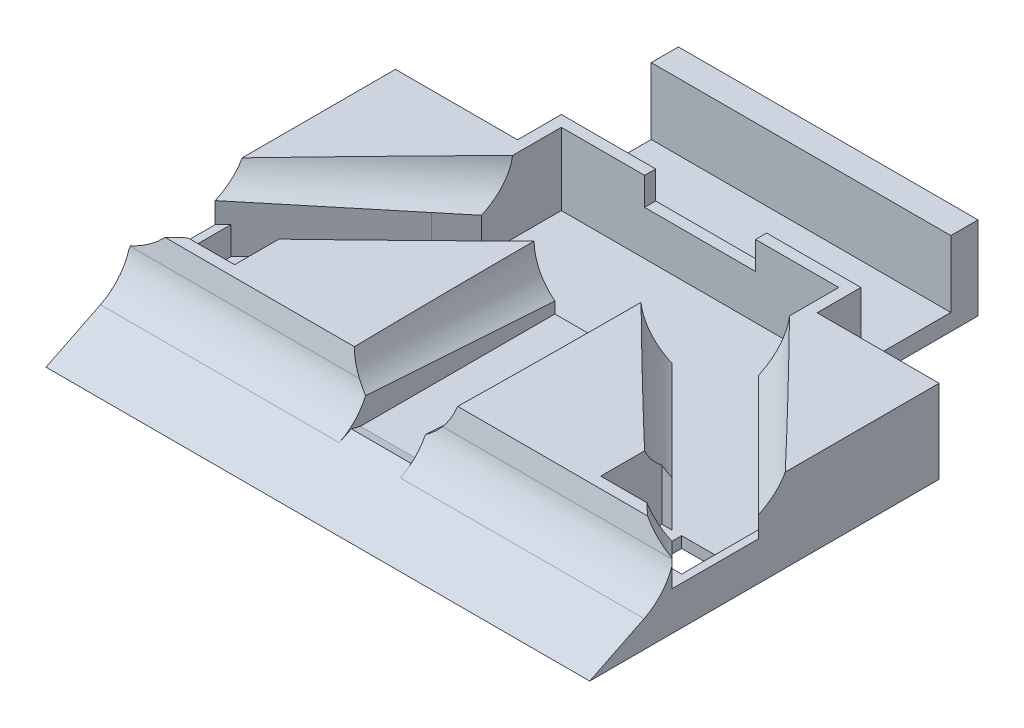
SolidWorks part; units mm, degrees
ref_plane "Front Plane" through (0, 0, 0) normal (0, 0, 1) x (1, 0, 0)
ref_plane "Top Plane" through (0, 0, 0) normal (0, 1, 0) x (1, 0, 0)
ref_plane "Right Plane" through (0, 0, 0) normal (1, 0, 0) x (0, 0, -1)
sketch "Sketch1" plane through (0, 0, 0) normal (0, 1, 0) x (1, 0, 0)
  line L1 (-41.0843, 19.8343) -> (56.9157, 19.8343)
  line L2 (-41.0843, 19.8343) -> (-41.0843, -70.1657)
  line L3 (-41.0843, -70.1657) -> (56.9157, -70.1657)
  line L4 (56.9157, 19.8343) -> (56.9157, -70.1657)
  dimension "D1" = 98
  dimension "D2" = 90
extrude "Boss-Extrude1" add sketch "Sketch1" along normal blind 15
sketch "Sketch3" plane through (0, 15, 0) normal (0, 1, 0) x (1, 0, 0)
  line L0 (-41.0843, -35.1657) -> (-6.0843, -70.1657)
  line L1 (-41.0843, 19.8343) -> (-41.0843, -70.1657) construction
  line L2 (-41.0843, -70.1657) -> (56.9157, -70.1657) construction
  line L3 (-6.0843, -70.1657) -> (-41.0843, -70.1657)
  line L4 (-41.0843, -70.1657) -> (-41.0843, -35.1657)
  line L5 (21.9157, -70.1657) -> (56.9157, -35.1657)
  line L6 (56.9157, -70.1657) -> (56.9157, 19.8343) construction
  line L7 (56.9157, -35.1657) -> (56.9157, -70.1657)
  line L8 (56.9157, -70.1657) -> (21.9157, -70.1657)
  dimension "D1" = 35
  dimension "D2" = 35
  dimension "D3" = 35
extrude "Cut-Extrude1" cut sketch "Sketch3" against normal blind 15
sketch "Sketch4" plane through (0, 15, 0) normal (0, 1, 0) x (1, 0, 0)
  line L0 (-41.0843, -35.1657) -> (-32.2419, -26.3233)
  line L1 (-32.2419, -26.3233) -> (-41.0843, -17.4808)
  line L2 (-41.0843, 19.8343) -> (-41.0843, -35.1657) construction
  line L3 (-41.0843, -17.4808) -> (-41.0843, -35.1657)
  line L4 (56.9157, -17.4808) -> (48.0733, -26.3233)
  line L5 (56.9157, -35.1657) -> (56.9157, 19.8343) construction
  line L6 (48.0733, -26.3233) -> (56.9157, -35.1657)
  line L7 (56.9157, -35.1657) -> (56.9157, -17.4808)
extrude "Cut-Extrude2" cut sketch "Sketch4" against normal blind 15
sketch "Sketch5" plane through (-2.9593, 0, -2.9593) normal (-0.7071, 0, -0.7071) x (-0.7071, 0, 0.7071)
  line L0 (53.9169, 0) -> (52.9169, 15)
  line L1 (53.9169, 15) -> (41.4118, 15) construction
  line L2 (53.9169, 15) -> (52.9169, 15)
  line L4 (53.9169, 15) -> (53.9169, 0)
  dimension "D1" = 1
extrude "Cut-Extrude5" cut sketch "Sketch5" against normal blind 100
sketch "Sketch8" plane through (10.875, 0, -10.875) normal (0.7071, 0, -0.7071) x (-0.7071, 0, -0.7071)
  line L0 (-65.1114, 0) -> (-64.1114, 15)
  line L1 (-52.6063, 15) -> (-65.1114, 15) construction
  line L2 (-64.1114, 15) -> (-65.1114, 15)
  line L3 (-65.1114, 15) -> (-65.1114, 0)
  dimension "D1" = 1
extrude "Cut-Extrude6" cut sketch "Sketch8" against normal blind 100
sketch "Sketch9" plane through (45.837, 4.3215, 45.837) normal (0.7055, 0.0665, 0.7055) x (0.7087, -0.0662, -0.7024)
  line L0 (15.6331, -3.3008) -> (-33.7552, -6.5861) construction
  circle A0 centre (-0.3647, 13.6748) radius 9.5
  dimension "D1" = 18
  dimension "D2" = 15
extrude "Cut-Extrude7" cut sketch "Sketch9" against normal blind 45
sketch "Sketch10" plane through (-37.9563, 3.5786, 37.9563) normal (-0.7055, 0.0665, 0.7055) x (0.7087, 0.0662, 0.7024)
  line L0 (44.9744, -6.5861) -> (-4.4139, -3.3008) construction
  circle A0 centre (11.452, 13.6836) radius 9.5
  dimension "D1" = 18
  dimension "D2" = 15
extrude "Cut-Extrude8" cut sketch "Sketch10" against normal blind 45
sketch "Sketch12" plane through (10.875, 0, -10.875) normal (0.7071, 0, -0.7071) x (-0.7071, 0, -0.7071)
  line L0 (-65.1114, 0) -> (-64.1114, 15)
  line L1 (-64.1114, 15) -> (-65.1114, 15)
  line L2 (-65.1114, 15) -> (-65.1114, 0)
  dimension "D1" = 1
extrude "Boss-Extrude3" add sketch "Sketch12" against normal blind 100
sketch "Sketch13" plane through (-2.9593, 0, -2.9593) normal (-0.7071, 0, -0.7071) x (-0.7071, 0, 0.7071)
  line L0 (53.9169, 0) -> (52.9169, 15)
  line L1 (52.9169, 15) -> (53.9169, 15)
  line L2 (53.9169, 15) -> (53.9169, 0)
  dimension "D1" = 1
extrude "Boss-Extrude4" add sketch "Sketch13" against normal blind 100
sketch "Sketch14" plane through (0, 15, 0) normal (0, 1, 0) x (1, 0, 0)
  line L1 (-6.0843, -70.1657) -> (48.4536, -70.1657)
  line L2 (-6.0843, -70.1657) -> (-6.0843, -107.5994)
  line L3 (-6.0843, -107.5994) -> (48.4536, -107.5994)
  line L4 (48.4536, -70.1657) -> (48.4536, -107.5994)
extrude "Cut-Extrude9" cut sketch "Sketch14" against normal blind 100
sketch "Sketch15" plane through (0, 15, 0) normal (0, 1, 0) x (1, 0, 0)
  line L2 (3.5432, -108.6479) -> (-33.6782, -108.6479)
  line L3 (3.5432, -108.6479) -> (3.5432, -76.6689)
  line L4 (3.5432, -76.6689) -> (-33.6782, -76.6689)
  line L5 (-33.6782, -108.6479) -> (-33.6782, -76.6689)
extrude "Cut-Extrude10" cut sketch "Sketch15" against normal blind 100
sketch "Sketch16" plane through (0, 15, 0) normal (0, 1, 0) x (1, 0, 0)
  line L0 (-6.0843, -70.1657) -> (-35.8986, -70.1657)
  line L1 (-41.0843, -35.1657) -> (-41.0843, -70.1657)
  line L2 (-41.0843, -70.1657) -> (-35.8986, -70.1657)
  line L3 (-41.0843, -35.1657) -> (-6.0843, -70.1657)
extrude "Boss-Extrude5" add sketch "Sketch16" against normal blind 15
sketch "Sketch17" plane through (0, 15, 0) normal (0, 1, 0) x (1, 0, 0)
  line L0 (21.9157, -70.1657) -> (49.8862, -70.1657)
  line L1 (56.9157, -35.1657) -> (56.9157, -70.1657)
  line L2 (56.9157, -70.1657) -> (49.8862, -70.1657)
  line L3 (21.9157, -70.1657) -> (56.9157, -35.1657)
extrude "Boss-Extrude6" add sketch "Sketch17" against normal blind 15
sketch "Sketch18" plane through (0, 15, 0) normal (0, 1, 0) x (1, 0, 0)
  line L0 (48.0733, -26.3233) -> (56.9157, -17.4808)
  line L1 (56.9157, -17.4808) -> (56.9157, -35.1657)
  line L2 (56.9157, -35.1657) -> (48.0733, -26.3233)
  line L3 (-41.0843, -35.1657) -> (-41.0843, -17.4808)
  line L4 (-41.0843, -17.4808) -> (-32.2419, -26.3233)
  line L5 (-32.2419, -26.3233) -> (-41.0843, -35.1657)
extrude "Boss-Extrude7" add sketch "Sketch18" against normal blind 15
sketch "Sketch19" plane through (56.9157, 0, 0) normal (1, 0, 0) x (0, 0, -1)
  line L0 (-70.1657, 0) -> (-69.1657, 15)
  line L1 (-70.1657, 15) -> (19.8343, 15) construction
  line L2 (-70.1657, 15) -> (-69.1657, 15)
  line L3 (-70.1657, 15) -> (-70.1657, 0)
  dimension "D1" = 1
extrude "Cut-Extrude11" cut sketch "Sketch19" against normal blind 100
sketch "Sketch20" plane through (0, 4.657, 69.8552) normal (0, 0.0665, 0.9978) x (1, 0, 0)
  line L0 (-41.0843, -4.6674) -> (56.9157, -4.6674) construction
  circle A0 centre (7.9157, 13.3326) radius 9.5
  point P2 (7.9157, -4.6674)
  dimension "D1" = 49
  dimension "D2" = 18
extrude "Cut-Extrude12" cut sketch "Sketch20" against normal blind 45
sketch "Sketch21" plane through (14.0876, 1.3282, 14.0876) normal (0.7055, 0.0665, 0.7055) x (0.7087, -0.0662, -0.7024)
  line L0 (-8.7092, 13.1531) -> (9.1121, 14.3386) construction
  circle A0 centre (2.2015, 13.8789) radius 9.5
  point P4 (0.2015, 13.7458)
  dimension "D1" = 2
extrude "Cut-Extrude13" cut sketch "Sketch21" along normal blind 100
sketch "Sketch22" plane through (14.0876, 1.3282, 14.0876) normal (0.7055, 0.0665, 0.7055) x (0.7087, -0.0662, -0.7024)
  circle A0 centre (-0.3647, 13.6748) radius 9.5
extrude "Boss-Extrude8" add sketch "Sketch22" along normal blind 55
sketch "Sketch23" plane through (52.8924, 4.9867, 52.8924) normal (0.7055, 0.0665, 0.7055) x (0.7024, 0.0662, -0.7087)
  circle A0 centre (4.0203, 13.465) radius 9.5
extrude "Cut-Extrude14" cut sketch "Sketch23" against normal blind 55
sketch "Sketch24" plane through (-6.207, 0.5852, 6.207) normal (-0.7055, 0.0665, 0.7055) x (0.7087, 0.0662, 0.7024)
  line L0 (1.9753, 14.3473) -> (19.9284, 13.1531) construction
  circle A0 centre (8.9518, 13.8833) radius 9.5
  point P4 (10.9518, 13.7502)
  dimension "D1" = 2
extrude "Cut-Extrude15" cut sketch "Sketch24" along normal blind 100
sketch "Sketch25" plane through (-6.207, 0.5852, 6.207) normal (-0.7055, 0.0665, 0.7055) x (0.7087, 0.0662, 0.7024)
  circle A0 centre (11.452, 13.6836) radius 9.5
extrude "Boss-Extrude10" add sketch "Sketch25" along normal blind 100
sketch "Sketch26" plane through (-6.207, 0.5852, 6.207) normal (-0.7055, 0.0665, 0.7055) x (0.7087, 0.0662, 0.7024)
  circle A0 centre (8.9518, 13.8833) radius 9.5
extrude "Cut-Extrude16" cut sketch "Sketch26" along normal blind 100
sketch "Sketch27" plane through (0, 15, 0) normal (0, 1, 0) x (1, 0, 0)
  line L1 (-41.0843, 19.8343) -> (56.9157, 19.8343)
  line L2 (-41.0843, 19.8343) -> (-41.0843, -70.1657)
  line L3 (-41.0843, -70.1657) -> (56.9157, -70.1657)
  line L4 (56.9157, 19.8343) -> (56.9157, -70.1657)
  line L5 (92.056, -99.7406) -> (-84.3219, -99.7406)
  line L6 (92.056, -99.7406) -> (92.056, 23.1019)
  line L7 (92.056, 23.1019) -> (-84.3219, 23.1019)
  line L8 (-84.3219, -99.7406) -> (-84.3219, 23.1019)
extrude "Cut-Extrude19" cut sketch "Sketch27" against normal blind 100 and the other way blind 100
sketch "Sketch28" plane through (0, 0, -19.8343) normal (0, 0, -1) x (-1, 0, 0)
  line L1 (-56.9157, 15) -> (52.5951, 15)
  line L2 (-56.9157, 15) -> (-56.9157, 39.112)
  line L3 (-56.9157, 39.112) -> (52.5951, 39.112)
  line L4 (52.5951, 15) -> (52.5951, 39.112)
extrude "Cut-Extrude20" cut sketch "Sketch28" against normal blind 100
sketch "Sketch29" plane through (0, 1.6637, 24.9549) normal (0, 0.0665, 0.9978) x (1, 0, 0)
  line L0 (4.234, 13.3659) -> (11.41, 13.3659) construction
  circle A0 centre (7.822, 13.3659) radius 9.5994
extrude "Cut-Extrude21" cut sketch "Sketch29" along normal blind 100
sketch "Sketch30" plane through (0, 15, 0) normal (0, 1, 0) x (1, 0, 0)
  line L1 (-41.0843, 19.8343) -> (-19.0843, 19.8343)
  line L2 (-41.0843, 19.8343) -> (-41.0843, -12.1657)
  line L3 (-41.0843, -12.1657) -> (-19.0843, -12.1657)
  line L4 (-19.0843, 19.8343) -> (-19.0843, -12.1657)
  line L5 (56.9157, 19.8343) -> (34.9157, 19.8343)
  line L6 (56.9157, 19.8343) -> (56.9157, -12.1657)
  line L7 (56.9157, -12.1657) -> (34.9157, -12.1657)
  line L8 (34.9157, 19.8343) -> (34.9157, -12.1657)
  dimension "D1" = 22
  dimension "D2" = 32
  dimension "D3" = 22
extrude "Cut-Extrude22" cut sketch "Sketch30" against normal blind 100
sketch "Sketch31" plane through (34.9157, 0, 0) normal (1, 0, 0) x (0, 0, -1)
  line L0 (19.8343, 15) -> (-12.1657, 15) construction
  line L1 (-4.2657, 15) -> (11.9343, 15)
  line L2 (-4.2657, 15) -> (-4.2657, 3)
  line L3 (-4.2657, 3) -> (11.9343, 3)
  line L4 (11.9343, 15) -> (11.9343, 3)
  dimension "D1" = 16.2
  dimension "D2" = 12
  dimension "D3" = 7.9
  dimension "D4" = 7.9
extrude "Cut-Extrude23" cut sketch "Sketch31" against normal blind 100
sketch "Sketch32" plane through (0, 15, 0) normal (0, 1, 0) x (1, 0, 0)
  line L0 (34.9157, -4.2657) -> (34.9157, -12.1657) construction
  line L1 (-1.776, -26.4909) -> (32.9157, -26.4909)
  line L2 (-19.0843, -4.2657) -> (34.9157, -4.2657) construction
  line L3 (-1.776, -6.2657) -> (32.9157, -6.2657)
  line L4 (32.9157, -26.4909) -> (32.9157, -6.2657)
  line L5 (-1.776, -26.4909) -> (-17.0843, -26.4909)
  line L6 (-19.0843, -12.1657) -> (-19.0843, -4.2657) construction
  line L7 (-1.776, -6.2657) -> (-17.0843, -6.2657)
  line L8 (-17.0843, -26.4909) -> (-17.0843, -6.2657)
  dimension "D1" = 2
  dimension "D2" = 2
  dimension "D3" = 2
extrude "Cut-Extrude24" cut sketch "Sketch32" against normal blind 13
sketch "Sketch33" plane through (0, 15, 0) normal (0, 1, 0) x (1, 0, 0)
  line L0 (-19.0843, -4.2657) -> (34.9157, -4.2657) construction
  line L1 (32.9157, -6.2657) -> (-17.4573, -6.2657)
  line L2 (32.9157, -6.2657) -> (32.9157, -4.2657)
  line L3 (32.9157, -4.2657) -> (-17.4573, -4.2657)
  line L4 (-17.4573, -6.2657) -> (-17.4573, -4.2657)
extrude "Boss-Extrude12" add sketch "Sketch33" against normal blind 15
sketch "Sketch34" plane through (0, 15, 0) normal (0, 1, 0) x (1, 0, 0)
  line L0 (-19.0843, -4.2657) -> (34.9157, -4.2657) construction
  line L1 (-2.0843, -4.2657) -> (17.9157, -4.2657)
  line L2 (-2.0843, -4.2657) -> (-2.0843, -6.2657)
  line L3 (-2.0843, -6.2657) -> (17.9157, -6.2657)
  line L4 (17.9157, -4.2657) -> (17.9157, -6.2657)
  line L5 (32.9157, -6.2657) -> (-17.0843, -6.2657) construction
  dimension "D1" = 20
  dimension "D2" = 17
  dimension "D3" = 17
extrude "Cut-Extrude25" cut sketch "Sketch34" against normal blind 5
sketch "Sketch35" plane through (56.9157, 0, 0) normal (1, 0, 0) x (0, 0, -1)
  line L0 (-70.1657, 0) -> (-62.1657, 3)
  line L1 (-62.1657, 3) -> (-59.1657, 15)
  line L2 (-26.4909, 15) -> (-64.3833, 15) construction
  line L3 (-59.1657, 15) -> (-69.1657, 15)
  line L4 (-69.1657, 15) -> (-70.1657, 0)
  line L5 (-70.1657, 0) -> (-12.1657, 0) construction
  dimension "D1" = 8
  dimension "D2" = 10
  dimension "D3" = 3
extrude "Cut-Extrude27" cut sketch "Sketch35" against normal blind 100
sketch "Sketch37" plane through (0, 15, 0) normal (0, 1, 0) x (1, 0, 0)
  line L0 (-41.0843, -39.8067) -> (-41.0843, -60.0609) construction
  line L1 (-25.0843, -57.1657) -> (-39.0843, -57.1657)
  line L2 (-25.0843, -57.1657) -> (-25.0843, -46.1657)
  line L3 (-25.0843, -46.1657) -> (-39.0843, -46.1657)
  line L4 (-39.0843, -57.1657) -> (-39.0843, -46.1657)
  line L5 (-35.6105, -59.1657) -> (-1.4891, -59.1657) construction
  line L6 (56.9157, -60.071) -> (56.9157, -39.9025) construction
  line L7 (40.9157, -57.1657) -> (54.9157, -57.1657)
  line L8 (40.9157, -57.1657) -> (40.9157, -46.1657)
  line L9 (40.9157, -46.1657) -> (54.9157, -46.1657)
  line L10 (54.9157, -57.1657) -> (54.9157, -46.1657)
  dimension "D1" = 11
  dimension "D2" = 14
  dimension "D3" = 2
  dimension "D4" = 2
  dimension "D5" = 14
  dimension "D6" = 2
extrude "Cut-Extrude28" cut sketch "Sketch37" against normal blind 13
sketch "Sketch38" plane through (0, 15, 0) normal (0, 1, 0) x (1, 0, 0)
  line L0 (17.4201, -26.4909) -> (-1.776, -26.4909) construction
  line L1 (1.9784, -26.4909) -> (12.9784, -26.4909)
  line L2 (1.9784, -26.4909) -> (1.9784, -60.5857)
  line L4 (12.9784, -26.4909) -> (12.9784, -60.5857)
  line L7 (1.9784, -60.5857) -> (1.9784, -67.4408)
  line L8 (1.9784, -67.4408) -> (12.9784, -67.4408)
  line L9 (12.9784, -60.5857) -> (12.9784, -67.4408)
  ellipse E0 centre (7.822, -58.5903) end of major axis (17.4214, -58.5903) minor radius 2.3657 (-1.4891, -59.1657) -> (17.1332, -59.1657) ccw construction
  dimension "D1" = 11
extrude "Cut-Extrude32" cut sketch "Sketch38" against normal blind 9.5
sketch "Sketch39" plane through (0, 15, 0) normal (0, 1, 0) x (1, 0, 0)
  line L0 (-45.2196, -64.3228) -> (-13.7885, -32.9359)
  line L2 (-21.5612, -25.1522) -> (-52.9923, -56.5391)
  line L3 (-52.9923, -56.5391) -> (-45.2196, -64.3228)
  line L4 (-21.5612, -25.1522) -> (-11.6742, -15.2653)
  line L5 (-11.6742, -15.2653) -> (-3.8961, -23.0435)
  line L6 (-13.7885, -32.9359) -> (-3.8961, -23.0435)
  ellipse E0 centre (0.1369, -11.1918) end of major axis (101.1233, 89.7946) minor radius 9.5 (-17.0843, -15.0514) -> (-41.0843, -39.8067) ccw construction
  ellipse E1 centre (0.1369, -11.1918) end of major axis (101.1233, 89.7946) minor radius 9.5 (-25.0843, -49.1733) -> (-1.776, -26.4909) ccw construction
  point P2 (-29.1383, -27.3767)
  point P12 (-13.3844, -37.8792)
  point P20 (-13.3844, -37.8792)
  dimension "D1" = 11
  dimension "D2" = 3.78
extrude "Cut-Extrude33" cut sketch "Sketch39" against normal blind 13
sketch "Sketch40" plane through (0, 15, 0) normal (0, 1, 0) x (1, 0, 0)
  line L0 (61.0272, -64.4312) -> (18.7555, -22.1596)
  line L1 (18.7555, -22.1596) -> (26.5337, -14.3814)
  line L2 (26.5337, -14.3814) -> (68.8053, -56.653)
  line L3 (68.8053, -56.653) -> (61.0272, -64.4312)
  ellipse E0 centre (15.6477, -11.2385) end of major axis (-85.3387, 89.7479) minor radius 9.5 (56.9157, -39.9025) -> (32.9157, -15.1455) ccw construction
  ellipse E1 centre (15.6477, -11.2385) end of major axis (-85.3387, 89.7479) minor radius 9.5 (17.5134, -26.4909) -> (40.9157, -49.2648) ccw construction
  point P2 (44.9697, -27.4716)
  point P12 (29.1684, -37.9253)
  dimension "D1" = 11
  dimension "D2" = 3.78
extrude "Cut-Extrude34" cut sketch "Sketch40" against normal blind 13
sketch "Sketch41" plane through (0, 2, 0) normal (0, 1, 0) x (1, 0, 0)
  line L1 (56.9157, -60.3197) -> (56.9157, -44.7634)
  line L2 (56.9157, -44.7634) -> (55.5015, -43.3492)
  line L3 (56.9157, -44.7634) -> (32.9157, -20.7634) construction
  line L4 (55.5015, -43.3492) -> (55.5015, -58.9055)
  line L5 (53.7616, -57.1657) -> (56.9157, -60.3197) construction
  line L6 (55.5015, -58.9055) -> (56.9157, -60.3197)
  dimension "D1" = 2
extrude "Boss-Extrude18" add sketch "Sketch41" along normal blind 5
sketch "Sketch42" plane through (0, 2, 0) normal (0, 1, 0) x (1, 0, 0)
  line L0 (-41.0843, -44.6479) -> (-39.6691, -43.2347)
  line L1 (-21.5612, -25.1522) -> (-41.0843, -44.6479) construction
  line L2 (-41.0843, -44.6479) -> (-41.0843, -60.1934)
  line L3 (-41.0843, -60.1934) -> (-39.6691, -58.7801)
  line L4 (-41.0843, -60.1934) -> (-38.0524, -57.1657) construction
  line L5 (-39.6691, -58.7801) -> (-39.6691, -43.2347)
  dimension "D1" = 2
  dimension "D2" = 2
extrude "Boss-Extrude19" add sketch "Sketch42" along normal blind 5
sketch "Sketch43" plane through (56.9157, 0, 0) normal (1, 0, 0) x (0, 0, -1)
  line L0 (-62.1657, 3) -> (-75.1544, 0)
  line L1 (-62.1544, 0) -> (-75.1544, 0)
  line L2 (-70.1657, 0) -> (-12.1657, 0) construction
  line L3 (-62.1544, 0) -> (-62.1657, 3)
  dimension "D1" = 13
extrude "Boss-Extrude21" add sketch "Sketch43" against normal blind 98
sketch "Sketch45" plane through (56.9157, 0, 0) normal (1, 0, 0) x (0, 0, -1)
  line L0 (-75.1544, 0) -> (-61.5447, 5.484)
  line L1 (-62.1657, 3) -> (-60.3197, 10.3838) construction
  line L2 (-61.5447, 5.484) -> (-62.1657, 3)
  line L3 (-62.1657, 3) -> (-75.1544, 0) construction
  line L4 (-62.1657, 3) -> (-75.1544, 0)
extrude "Boss-Extrude22" add sketch "Sketch45" against normal blind 98
sketch "Sketch46" plane through (56.9157, 0, 0) normal (1, 0, 0) x (0, 0, -1)
  line L0 (-75.1544, 0) -> (-61.1931, 6.8905)
  line L1 (-61.5447, 5.484) -> (-60.3197, 10.3838) construction
  line L2 (-61.1931, 6.8905) -> (-61.5447, 5.484)
  line L3 (-61.5447, 5.484) -> (-75.1544, 0)
extrude "Boss-Extrude23" add sketch "Sketch46" against normal blind 98
sketch "Sketch47" plane through (0, 14.8037, 59.2148) normal (0, -0.2425, -0.9701) x (-1, 0, 0)
  line L0 (-1.9784, -8.1568) -> (-12.9784, -8.1568) construction
  line L1 (-12.9784, -9.59) -> (-1.9784, -9.59)
  line L2 (-12.9784, -9.59) -> (-12.9784, -8.1568)
  line L3 (-12.9784, -8.1568) -> (-1.9784, -8.1568)
  line L4 (-1.9784, -9.59) -> (-1.9784, -8.1568)
extrude "Cut-Extrude36" cut sketch "Sketch47" against normal blind 98
sketch "Sketch48" plane through (0, 2, 0) normal (0, 1, 0) x (1, 0, 0)
  line L0 (55.5015, -43.3492) -> (55.5015, -58.9055) construction
  line L1 (44.5015, -57.1657) -> (55.5015, -57.1657)
  line L2 (44.5015, -57.1657) -> (44.5015, -46.1657)
  line L3 (44.5015, -46.1657) -> (55.5015, -46.1657)
  line L4 (55.5015, -57.1657) -> (55.5015, -46.1657)
  line L7 (-39.6691, -58.7801) -> (-39.6691, -43.2347) construction
  line L8 (-39.6691, -57.1657) -> (-28.6691, -57.1657)
  line L9 (-39.6691, -57.1657) -> (-39.6691, -46.1657)
  line L10 (-39.6691, -46.1657) -> (-28.6691, -46.1657)
  line L11 (-28.6691, -57.1657) -> (-28.6691, -46.1657)
  dimension "D1" = 11
  dimension "D2" = 11
  dimension "D3" = 0
  dimension "D4" = 11
  dimension "D5" = 11
  dimension "D6" = 0
extrude "Cut-Extrude37" cut sketch "Sketch48" against normal blind 98
sketch "Sketch49" plane through (0, 2, 0) normal (0, 1, 0) x (1, 0, 0)
  line L0 (55.5015, -58.9055) -> (53.7616, -57.1657)
  line L1 (55.5015, -57.1657) -> (55.5015, -58.9055) construction
  line L2 (53.7616, -57.1657) -> (55.5015, -58.9055) construction
  line L3 (53.7616, -57.1657) -> (55.5015, -57.1657)
  line L4 (55.5015, -57.1657) -> (55.5015, -58.9055)
extrude "Boss-Extrude24" add sketch "Sketch49" along normal blind 5
sketch "Sketch50" plane through (0, 2, 0) normal (0, 1, 0) x (1, 0, 0)
  line L0 (-39.6691, -58.7801) -> (-39.6691, -57.1657)
  line L1 (-39.6691, -57.1657) -> (-38.0524, -57.1657)
  line L2 (-39.6691, -58.7801) -> (-38.0524, -57.1657) construction
  line L3 (-39.6691, -57.1657) -> (-38.0524, -57.1657) construction
  line L4 (-38.0524, -57.1657) -> (-39.6691, -58.7801)
extrude "Boss-Extrude25" add sketch "Sketch50" along normal blind 5
fillet "Fillet1" radius 10 2 edges at (-19.5529, 6.8905, 61.1931) (34.9471, 6.8905, 61.1931)
sketch "Sketch52" plane through (34.9157, 0, 0) normal (1, 0, 0) x (0, 0, -1)
  line L0 (19.8343, 15) -> (11.9343, 15) construction
  line L1 (16.8343, 15) -> (19.8343, 15)
  line L2 (16.8343, 15) -> (16.8343, 0)
  line L3 (16.8343, 0) -> (19.8343, 0)
  line L4 (19.8343, 15) -> (19.8343, 0)
  dimension "D1" = 3
extrude "Cut-Extrude39" cut sketch "Sketch52" against normal blind 100
